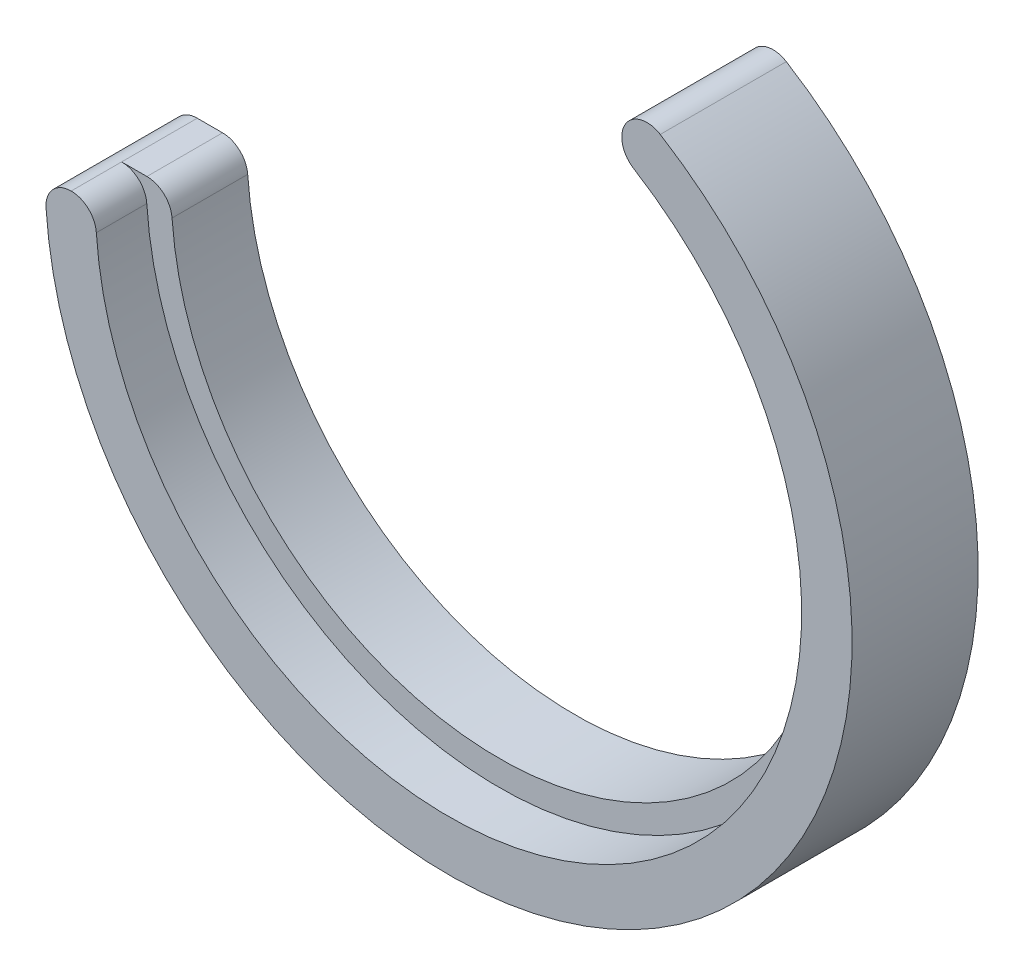
SolidWorks part; units mm, degrees
ref_plane "Front Plane" through (0, 0, 0) normal (0, 0, 1) x (1, 0, 0)
ref_plane "Top Plane" through (0, 0, 0) normal (0, 1, 0) x (1, 0, 0)
ref_plane "Right Plane" through (0, 0, 0) normal (1, 0, 0) x (0, 0, -1)
sketch "Sketch1" plane through (0, 0, 0) normal (0, 0, 1) x (1, 0, 0)
  line L0 (3.7329, 7.0757) -> (3.033, 5.749)
  line L1 (-8, 0) -> (-6.5, 0)
  arc A0 (3.033, 5.749) -> (-6.5, 0) centre (0, 0) cw
  arc A1 (3.7329, 7.0757) -> (-8, 0) centre (0, 0) cw
  dimension "D1" = 1.5
extrude "Boss-Extrude1" add sketch "Sketch1" along normal blind 1.5
ref_plane "Plane1" through (0, 0, 1.5) normal (0, 0, 1) x (1, 0, 0)
sketch "Sketch2" plane through (0, 0, 1.5) normal (0, 0, 1) x (1, 0, 0)
  line L2 (3.7329, 7.0757) -> (3.2663, 6.1912)
  line L3 (-7, 0) -> (-8, 0)
  arc A0 (3.2663, 6.1912) -> (-7, 0) centre (0, 0) cw
  arc A3 (3.7329, 7.0757) -> (-8, 0) centre (0, 0) cw
  dimension "D1" = 7
  dimension "D2" = 1
extrude "Boss-Extrude2" add sketch "Sketch2" along normal blind 1
fillet "Fillet1" radius 0.5 6 edges at (-6.5, 0, 0.75) (-8, 0, 1.25) (3.033, 5.749, 0.75) (3.7329, 7.0757, 1.25)
